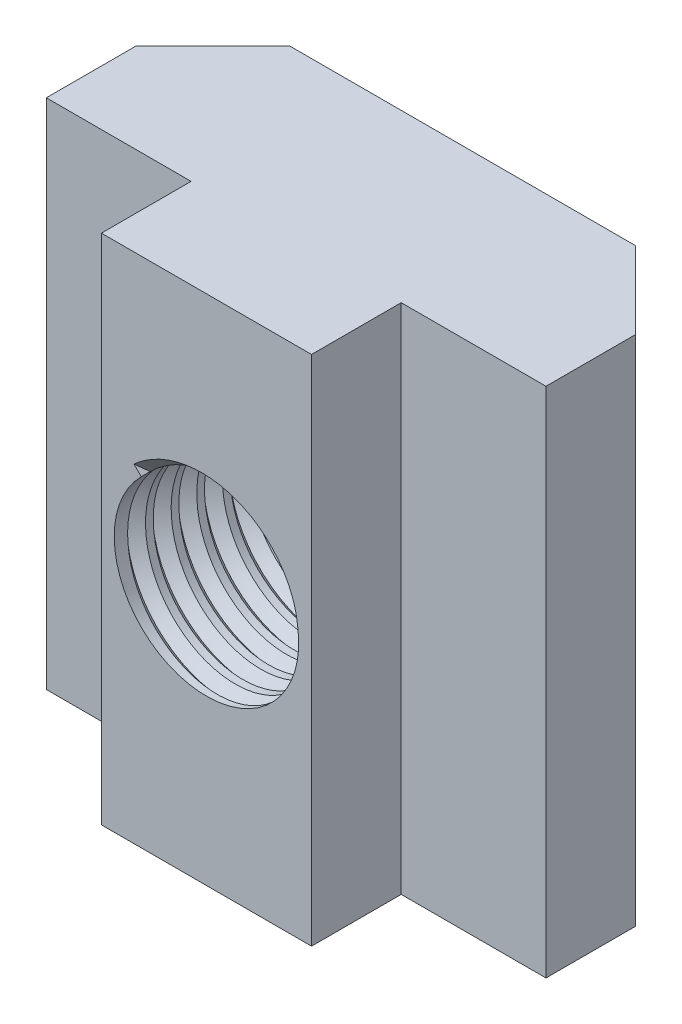
SolidWorks part; units mm, degrees
ref_plane "前视基准面" through (0, 0, 0) normal (0, 0, 1) x (1, 0, 0)
ref_plane "上视基准面" through (0, 0, 0) normal (0, 1, 0) x (1, 0, 0)
ref_plane "右视基准面" through (0, 0, 0) normal (1, 0, 0) x (0, 0, -1)
sketch "草图1" plane through (0, 0, 0) normal (0, 0, 1) x (1, 0, 0)
  line L1 (-9.75, -10) -> (9.75, -10)
  line L2 (-9.75, -10) -> (-9.75, 10)
  line L3 (-9.75, 10) -> (9.75, 10)
  line L4 (9.75, -10) -> (9.75, 10)
  line L5 (-9.75, -10) -> (9.75, 10) construction
  line L6 (-9.75, 10) -> (9.75, -10) construction
  point P0 (0, 0)
  dimension "D1" = 19.5
  dimension "D2" = 20
extrude "凸台-拉伸1" add sketch "草图1" along normal blind 6.5
sketch "草图2" plane through (0, 0, 6.5) normal (0, 0, 1) x (1, 0, 0)
  line L0 (9.75, 10) -> (-9.75, 10) construction
  line L1 (-4.1, -10) -> (4.1, -10)
  line L2 (-4.1, -10) -> (-4.1, 10)
  line L3 (-4.1, 10) -> (4.1, 10)
  line L4 (4.1, -10) -> (4.1, 10)
  line L5 (-4.1, -10) -> (4.1, 10) construction
  line L6 (-4.1, 10) -> (4.1, -10) construction
  point P0 (0, 0)
  dimension "D1" = 8.2
extrude "凸台-拉伸2" add sketch "草图2" along normal blind 3.5
chamfer "倒角1" distance 3 angle 45 2 edges at (9.75, 0, 0) (-9.75, 0, 0)
sketch "草图3" plane through (0, 0, 10) normal (0, 0, 1) x (1, 0, 0)
  circle A0 centre (0, 0) radius 3.6
  dimension "D1" = 7.2
extrude "切除-拉伸1" cut sketch "草图3" against normal through all
sketch "草图4" plane through (0, 0, 10) normal (0, 0, 1) x (1, 0, 0)
  circle A0 centre (0, 0) radius 3.6
curve "螺旋线/涡状线1" pitch 1 height 10 radius 3.6 centre (0, 0, 10) axis (0, 0, -1) start towards (-0.7071, 0.7071, 0)
sketch "草图5" plane through (0, 0, 0) normal (0, 1, 0) x (1, 0, 0)
  line L0 (3.6, -9.275) -> (3.6, -9.975)
  line L1 (3.6, -9.625) -> (4, -9.625) construction
  line L2 (3.6, -9.275) -> (4, -9.625)
  line L3 (4, -9.625) -> (3.6, -9.975)
  dimension "D1" = 0.7
  dimension "D2" = 0.4
sweep "切除-扫描1" cut profiles "草图5" path "螺旋线/涡状线1"
